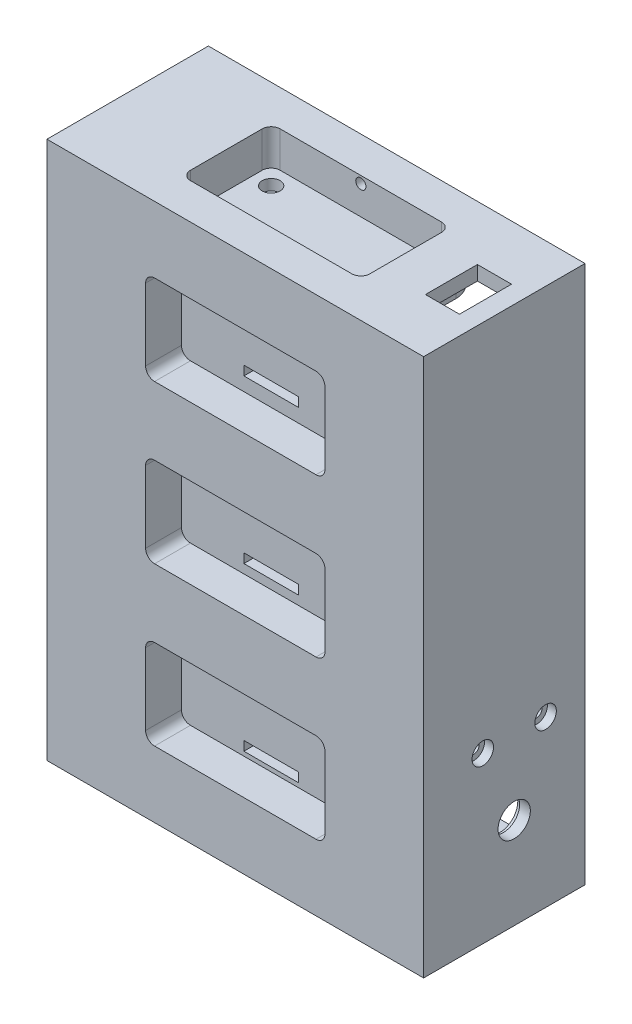
SolidWorks part; units mm, degrees
ref_plane "Спереди" through (0, 0, 0) normal (0, 0, 1) x (1, 0, 0)
ref_plane "Сверху" through (0, 0, 0) normal (0, 1, 0) x (1, 0, 0)
ref_plane "Справа" through (0, 0, 0) normal (1, 0, 0) x (0, 0, -1)
sketch "Эскиз1" plane through (0, 0, 0) normal (0, 0, 1) x (1, 0, 0)
  line L1 (-52.5, -75) -> (52.5, -75)
  line L2 (-52.5, -75) -> (-52.5, 75)
  line L3 (-52.5, 75) -> (52.5, 75)
  line L4 (52.5, -75) -> (52.5, 75)
  line L5 (-52.5, -75) -> (52.5, 75) construction
  line L6 (-52.5, 75) -> (52.5, -75) construction
  point P0 (0, 0)
  dimension "D1" = 105
  dimension "D2" = 150
extrude "Бобышка-Вытянуть1" add sketch "Эскиз1" along normal blind 45
sketch "Эскиз2" plane through (0, -75, 0) normal (0, -1, 0) x (1, 0, 0)
  line L0 (-1050, 22.5) -> (48950, 22.5) construction
  line L1 (-52.5, 45) -> (-52.5, 0) construction
  line L2 (0, -999.2777) -> (0, 49000.7223) construction
  line L4 (-22.5, 10) -> (22.5, 10)
  line L5 (-25, 12.5) -> (-25, 32.5)
  line L6 (-22.5, 35) -> (22.5, 35)
  line L7 (25, 12.5) -> (25, 32.5)
  line L8 (-25, 10) -> (25, 35) construction
  line L9 (-25, 35) -> (25, 10) construction
  arc A0 (-22.5, 35) -> (-25, 32.5) centre (-22.5, 32.5) ccw
  arc A1 (-25, 12.5) -> (-22.5, 10) centre (-22.5, 12.5) ccw
  arc A2 (25, 12.5) -> (22.5, 10) centre (22.5, 12.5) cw
  arc A3 (25, 32.5) -> (22.5, 35) centre (22.5, 32.5) ccw
  point P5 (-52.5, 22.5)
  point P6 (0, 22.5)
  point P12 (0, 22.5)
  dimension "D3" = 2.5
  dimension "D4" = 2.5
  dimension "D1" = 25
  dimension "D2" = 50
extrude "Вырез-Вытянуть1" cut sketch "Эскиз2" against normal blind 10
sketch "Эскиз4" plane through (0, 0, 45) normal (0, 0, 1) x (1, 0, 0)
  line L0 (0, -1000) -> (0, 49000) construction
  line L1 (-1000, 0) -> (49000, 0) construction
  line L2 (-22.5, 31.5) -> (22.5, 31.5)
  line L3 (-25, 34) -> (-25, 54)
  line L4 (-22.5, 56.5) -> (22.5, 56.5)
  line L5 (-22.5, -12.5) -> (22.5, -12.5)
  line L6 (-25, -10) -> (-25, 10)
  line L7 (-22.5, 12.5) -> (22.5, 12.5)
  line L8 (25, -10) -> (25, 10)
  line L9 (-25, -12.5) -> (25, 12.5) construction
  line L10 (-25, 12.5) -> (25, -12.5) construction
  line L11 (25, 34) -> (25, 54)
  line L12 (-25, 31.5) -> (25, 56.5) construction
  line L13 (-25, 56.5) -> (25, 31.5) construction
  line L14 (-25, -12.5) -> (25, -12.5) [skipped]
  line L15 (-25, -12.5) -> (-25, 12.5) [skipped]
  line L16 (-25, 12.5) -> (25, 12.5) [skipped]
  line L17 (25, -12.5) -> (25, 12.5) [skipped]
  line L18 (-25, -12.5) -> (25, 12.5) construction
  line L19 (-25, 12.5) -> (25, -12.5) construction
  line L20 (-22.5, -56.5) -> (22.5, -56.5)
  line L21 (-25, -54) -> (-25, -34)
  line L22 (-22.5, -31.5) -> (22.5, -31.5)
  line L23 (25, -54) -> (25, -34)
  line L24 (-25, -56.5) -> (25, -31.5) construction
  line L25 (-25, -31.5) -> (25, -56.5) construction
  arc A0 (22.5, -31.5) -> (25, -34) centre (22.5, -34) cw
  arc A1 (25, -54) -> (22.5, -56.5) centre (22.5, -54) cw
  arc A2 (-22.5, -56.5) -> (-25, -54) centre (-22.5, -54) cw
  arc A3 (-25, -34) -> (-22.5, -31.5) centre (-22.5, -34) cw
  arc A4 (-25, 54) -> (-22.5, 56.5) centre (-22.5, 54) cw
  arc A5 (-22.5, 12.5) -> (-25, 10) centre (-22.5, 10) ccw
  arc A6 (25, -10) -> (22.5, -12.5) centre (22.5, -10) cw
  arc A7 (22.5, 56.5) -> (25, 54) centre (22.5, 54) cw
  arc A8 (25, 34) -> (22.5, 31.5) centre (22.5, 34) cw
  arc A9 (-22.5, 31.5) -> (-25, 34) centre (-22.5, 34) cw
  arc A10 (22.5, 12.5) -> (25, 10) centre (22.5, 10) cw
  arc A11 (-22.5, -12.5) -> (-25, -10) centre (-22.5, -10) cw
  point P4 (25, 46.4046)
  point P6 (36.2514, -28.1819)
  point P7 (0, 0)
  point P8 (0, 0)
  point P9 (0, 44)
  point P18 (0, 0)
  point P23 (0, -44)
  point P28 (1.0897, -41.0449)
  point P29 (0, 43.0061)
  dimension "D7" = 2.5
  dimension "D8" = 2.5
  dimension "D1" = 25
  dimension "D2" = 50
  dimension "D5" = 31.5
  dimension "D6" = 31.5
  dimension "D3" = 2
  dimension "D4" = 2
extrude "Вырез-Вытянуть2" cut sketch "Эскиз4" against normal blind 10
mirror "Зеркальное отражение1" about plane through (0, 0, 0) normal (0, 1, 0) of "Вырез-Вытянуть1"
shell "Оболочка1" thickness 4 removed face at (0, 0, 0)
sketch "Эскиз5" plane through (-52.5, 0, 0) normal (-1, 0, 0) x (0, 0, 1)
  line L0 (-985.5789, -75) -> (49014.4211, -75) construction
  line L2 (-988.4344, -61) -> (49011.5656, -61) construction
  line L3 (45, -75) -> (0, -75) construction
  line L4 (-983.1093, -29) -> (49016.8907, -29) construction
  line L5 (0, 75) -> (0, -75) construction
  line L6 (19.75, -29) -> (19.75, -49.5) construction
  circle A0 centre (11, -29) radius 1.475
  circle A1 centre (28.5, -29) radius 1.475
  circle A2 centre (19.75, -49.5) radius 4.5
  dimension "D2" = 32
  dimension "D3" = 2.95
  dimension "D6" = 17.5
  dimension "D7" = 9
  dimension "D1" = 14
  dimension "D4" = 17.5
  dimension "D5" = 11
  dimension "D8" = 20.5
extrude "Вырез-Вытянуть3" cut sketch "Эскиз5" against normal blind 15
sketch "Эскиз6" plane through (-52.5, 0, 0) normal (-1, 0, 0) x (0, 0, 1)
  circle A0 centre (11, -29) radius 3
  circle A1 centre (28.5, -29) radius 3
  dimension "D1" = 6
  dimension "D2" = 17.5
extrude "Вырез-Вытянуть4" cut sketch "Эскиз6" against normal blind 2.5
sketch "Эскиз10" plane through (0, 0, 31) normal (0, 0, -1) x (-1, 0, 0)
  line L0 (-22.5, -27.5) -> (22.5, -27.5) construction
  line L1 (21, -27.5) -> (26, -27.5)
  line L2 (21, -27.5) -> (21, -64)
  line L3 (21, -64) -> (26, -64)
  line L4 (26, -27.5) -> (26, -64)
  line L5 (21, -27.5) -> (26, -64) construction
  line L6 (21, -64) -> (26, -27.5) construction
  line L7 (29, -34) -> (29, -54) construction
  point P4 (23.5, -45.75)
  dimension "D1" = 36.5
  dimension "D2" = 3
  dimension "D3" = 5
extrude "Вырез-Вытянуть15" cut sketch "Эскиз10" against normal blind 3 and the other way through all
sketch "Эскиз11" plane through (-48.5, 0, 0) normal (1, 0, 0) x (0, 0, -1)
  circle A0 centre (-19.75, -49.5) radius 5
  dimension "D1" = 10
extrude "Вырез-Вытянуть16" cut sketch "Эскиз11" against normal blind 1
mirror "Зеркальное отражение2" about plane through (0, 0, 0) normal (1, 0, 0) of "Вырез-Вытянуть16", "Вырез-Вытянуть15", "Вырез-Вытянуть4", "Вырез-Вытянуть3"
sketch "Эскиз12" plane through (0, 0, 6) normal (0, 0, -1) x (-1, 0, 0)
  line L0 (-1014.7864, -63) -> (48985.2136, -63) construction
  line L1 (21, -61) -> (-21, -61) construction
  line L2 (0, -1061) -> (0, 48939) construction
  line L3 (-10, -1061) -> (-10, 48939) construction
  line L4 (10, -1061) -> (10, 48939) construction
  circle A0 centre (-10, -63) radius 1.45
  circle A1 centre (10, -63) radius 1.45
  point P7 (0, -61)
  point P15 (10, -63)
  dimension "D4" = 2.9
  dimension "D1" = 2
  dimension "D2" = 20
  dimension "D3" = 10
extrude "Вырез-Вытянуть17" cut sketch "Эскиз12" against normal blind 10
sketch "Эскиз13" plane through (0, 0, 31) normal (0, 0, -1) x (-1, 0, 0)
  line L0 (-1008.6674, -29.5) -> (48991.3326, -29.5) construction
  line L1 (-22.5, -27.5) -> (22.5, -27.5) construction
  line L2 (0, -1027.5) -> (0, 48972.5) construction
  circle A0 centre (-9, -29.5) radius 1.45
  circle A1 centre (9, -29.5) radius 1.45
  point P7 (0, -27.5)
  dimension "D2" = 18
  dimension "D3" = 2.9
  dimension "D1" = 2
  dimension "D4" = 18
extrude "Вырез-Вытянуть18" cut sketch "Эскиз13" against normal blind 10
sketch "Эскиз14" plane through (0, 0, 31) normal (0, 0, -1) x (-1, 0, 0)
  line L0 (20, -957.2029) -> (20, 49042.7971) construction
  line L1 (29, 54) -> (29, 34) construction
  line L2 (-22.5, 60.5) -> (22.5, 60.5) construction
  line L3 (0, -972.5) -> (0, 49027.5) construction
  line L4 (22.5, 27.5) -> (-22.5, 27.5) construction
  line L5 (-20, -957.2029) -> (-20, 49042.7971) construction
  circle A0 centre (20, 48.5) radius 1.45
  circle A1 centre (20, -6.5) radius 1.45
  circle A2 centre (-20, -6.5) radius 1.45
  circle A3 centre (-20, 48.5) radius 1.45
  point P15 (0, 27.5)
  dimension "D1" = 2.9
  dimension "D3" = 9
  dimension "D2" = 55
  dimension "D4" = 12
extrude "Вырез-Вытянуть19" cut sketch "Эскиз14" against normal blind 3
sketch "Эскиз15" plane through (0, 0, 35) normal (0, 0, 1) x (1, 0, 0)
  line L0 (-1010.1672, -54) -> (48989.8328, -54) construction
  line L1 (0, -1031.5) -> (0, 48968.5) construction
  line L2 (-7.6, -55.3) -> (7.6, -55.3)
  line L3 (-7.6, -55.3) -> (-7.6, -52.7)
  line L4 (-7.6, -52.7) -> (7.6, -52.7)
  line L5 (7.6, -55.3) -> (7.6, -52.7)
  line L6 (-7.6, -55.3) -> (7.6, -52.7) construction
  line L7 (-7.6, -52.7) -> (7.6, -55.3) construction
  line L8 (22.5, -31.5) -> (-22.5, -31.5) construction
  line L9 (-22.5, -56.5) -> (22.5, -56.5) construction
  line L10 (-7.6, -10) -> (7.6, -10)
  line L11 (-7.6, -10) -> (-7.6, -7.4)
  line L12 (-7.6, -7.4) -> (7.6, -7.4)
  line L13 (7.6, -10) -> (7.6, -7.4)
  line L14 (-7.6, -10) -> (7.6, -7.4) construction
  line L15 (-7.6, -7.4) -> (7.6, -10) construction
  line L16 (-7.6, 35.3) -> (7.6, 35.3)
  line L17 (-7.6, 35.3) -> (-7.6, 37.9)
  line L18 (-7.6, 37.9) -> (7.6, 37.9)
  line L19 (7.6, 35.3) -> (7.6, 37.9)
  line L20 (-7.6, 35.3) -> (7.6, 37.9) construction
  line L21 (-7.6, 37.9) -> (7.6, 35.3) construction
  line L22 (-22.5, -12.5) -> (22.5, -12.5) construction
  line L23 (22.5, 12.5) -> (-22.5, 12.5) construction
  circle A0 centre (-20, -36.5) radius 2.5
  circle A1 centre (20, -36.5) radius 2.5
  circle A2 centre (-20, 7.5) radius 2.5
  circle A3 centre (20, 7.5) radius 2.5
  circle A4 centre (-20, 51.5) radius 2.5
  circle A5 centre (20, 51.5) radius 2.5
  point P1 (0, -54)
  point P12 (0, -31.5)
  point P16 (0, -8.7)
  point P21 (0, 36.6)
  point P30 (-20, 7.508)
  dimension "D6" = 40
  dimension "D8" = 5
  dimension "D1" = 2.6
  dimension "D2" = 15.2
  dimension "D3" = 2.5
  dimension "D4" = 3
  dimension "D5" = 2.5
  dimension "D7" = 40
  dimension "D9" = 5
  dimension "D10" = 3
  dimension "D11" = 5
extrude "Вырез-Вытянуть20" cut sketch "Эскиз15" against normal blind 3
sketch "Эскиз16" plane through (0, 0, 32) normal (0, 0, 1) x (1, 0, 0)
  line L0 (-7.6, -54) -> (7.6, -54) construction
  line L1 (-7.6, -52.7) -> (-7.6, -55.3) construction
  line L2 (7.6, -55.3) -> (7.6, -52.7) construction
  line L3 (0, -1000) -> (0, 49000) construction
  line L4 (-7, -54.9) -> (7, -54.9)
  line L5 (-7, -54.9) -> (-7, -53.1)
  line L6 (-7, -53.1) -> (7, -53.1)
  line L7 (7, -54.9) -> (7, -53.1)
  line L8 (-7, -54.9) -> (7, -53.1) construction
  line L9 (-7, -53.1) -> (7, -54.9) construction
  line L10 (-7, -9.6) -> (7, -9.6)
  line L11 (-7, -9.6) -> (-7, -7.8)
  line L12 (-7, -7.8) -> (7, -7.8)
  line L13 (7, -9.6) -> (7, -7.8)
  line L14 (-7.6, -8.7) -> (7.6, -8.7) construction
  line L15 (-7, -9.6) -> (7, -7.8) construction
  line L16 (-7, -7.8) -> (7, -9.6) construction
  line L17 (-7, 35.7) -> (7, 35.7)
  line L18 (-7, 35.7) -> (-7, 37.5)
  line L19 (-7, 37.5) -> (7, 37.5)
  line L20 (7, 35.7) -> (7, 37.5)
  line L21 (-7.6, 36.6) -> (7.6, 36.6) construction
  line L22 (-7, 35.7) -> (7, 37.5) construction
  line L23 (-7, 37.5) -> (7, 35.7) construction
  line L24 (-7.6, -7.4) -> (-7.6, -10) construction
  point P6 (0, -54)
  point P12 (0, -30.9154)
  point P17 (0, -8.7)
  point P24 (0, 36.6)
  point P29 (0, -14.6748)
  point P30 (0, -9.0247)
  point P31 (-7.6, -8.7)
  dimension "D1" = 1.8
  dimension "D2" = 14
  dimension "D3" = 3
extrude "Вырез-Вытянуть21" cut sketch "Эскиз16" against normal blind 3
sketch "Эскиз17" plane through (0, -65, 0) normal (0, -1, 0) x (1, 0, 0)
  line L0 (-7.6, 12.5) -> (7.6, 12.5)
  line L1 (-7.6, 12.5) -> (-7.6, 15.1)
  line L2 (-7.6, 15.1) -> (7.6, 15.1)
  line L3 (7.6, 12.5) -> (7.6, 15.1)
  line L4 (-7.6, 12.5) -> (7.6, 15.1) construction
  line L5 (-7.6, 15.1) -> (7.6, 12.5) construction
  line L6 (-22.5, 10) -> (22.5, 10) construction
  line L7 (22.5, 35) -> (-22.5, 35) construction
  line L9 (0, -965) -> (0, 49035) construction
  line L10 (22.5, 35) -> (-22.5, 35) construction
  circle A0 centre (-20, 30) radius 2.5
  circle A1 centre (20, 30) radius 2.5
  point P0 (0, 13.8)
  point P13 (0, 13.8)
  point P14 (-8.8823, 15.1)
  point P16 (0, 13.8)
  point P20 (0, 35)
  dimension "D5" = 5
  dimension "D1" = 2.6
  dimension "D2" = 15.2
  dimension "D3" = 40
  dimension "D4" = 40
  dimension "D6" = 2.5
  dimension "D7" = 5
extrude "Вырез-Вытянуть22" cut sketch "Эскиз17" against normal blind 3
sketch "Эскиз18" plane through (0, -62, 0) normal (0, -1, 0) x (1, 0, 0)
  line L0 (-7.6, 13.8) -> (7.6, 13.8) construction
  line L1 (-7.6, 15.1) -> (-7.6, 12.5) construction
  line L2 (7.6, 12.5) -> (7.6, 15.1) construction
  line L4 (-7, 12.9) -> (7, 12.9)
  line L5 (-7, 12.9) -> (-7, 14.7)
  line L6 (-7, 14.7) -> (7, 14.7)
  line L7 (7, 12.9) -> (7, 14.7)
  line L8 (-7, 12.9) -> (7, 14.7) construction
  line L9 (-7, 14.7) -> (7, 12.9) construction
  point P6 (0, 13.8)
  dimension "D1" = 1.8
  dimension "D2" = 14
extrude "Вырез-Вытянуть23" cut sketch "Эскиз18" against normal blind 3
sketch "Эскиз19" plane through (0, 65, 0) normal (0, 1, 0) x (1, 0, 0)
  line L0 (-7.6, -32.5) -> (7.6, -32.5)
  line L1 (-7.6, -32.5) -> (-7.6, -29.9)
  line L2 (-7.6, -29.9) -> (7.6, -29.9)
  line L3 (7.6, -32.5) -> (7.6, -29.9)
  line L4 (-7.6, -32.5) -> (7.6, -29.9) construction
  line L5 (-7.6, -29.9) -> (7.6, -32.5) construction
  line L6 (0, -1010) -> (0, 48990) construction
  line L7 (-22.5, -10) -> (22.5, -10) construction
  line L8 (22.5, -35) -> (-22.5, -35) construction
  circle A0 centre (-20, -15) radius 2.5
  circle A1 centre (20, -15) radius 2.5
  point P0 (0, -31.2)
  point P14 (0, -10)
  point P16 (0, -31.2)
  point P17 (0, 0)
  dimension "D5" = 5
  dimension "D7" = 5
  dimension "D1" = 2.6
  dimension "D2" = 15.2
  dimension "D3" = 40
  dimension "D4" = 40
  dimension "D6" = 2.5
extrude "Вырез-Вытянуть24" cut sketch "Эскиз19" against normal blind 3
sketch "Эскиз20" plane through (0, 62, 0) normal (0, 1, 0) x (1, 0, 0)
  line L0 (-1007.6, -31.2) -> (48992.4, -31.2) construction
  line L1 (-7.6, -29.9) -> (-7.6, -32.5) construction
  line L3 (-7, -32.1) -> (7, -32.1)
  line L4 (-7, -32.1) -> (-7, -30.3)
  line L5 (-7, -30.3) -> (7, -30.3)
  line L6 (7, -32.1) -> (7, -30.3)
  line L7 (-7, -32.1) -> (7, -30.3) construction
  line L8 (-7, -30.3) -> (7, -32.1) construction
  line L10 (0, -1029.9) -> (0, 48970.1) construction
  line L11 (7.6, -29.9) -> (-7.6, -29.9) construction
  point P1 (0, -31.2)
  point P5 (-7.6, -31.2)
  point P10 (0, -31.2)
  point P18 (0, -29.9)
  dimension "D1" = 1.8
  dimension "D2" = 14
extrude "Вырез-Вытянуть25" cut sketch "Эскиз20" against normal blind 3
sketch "Эскиз21" plane through (0, 75, 0) normal (0, 1, 0) x (1, 0, 0)
  line L0 (-975, -22.5) -> (49025, -22.5) construction
  line L1 (37.75, -29.75) -> (47.25, -29.75)
  line L2 (37.75, -29.75) -> (37.75, -15.25)
  line L3 (37.75, -15.25) -> (47.25, -15.25)
  line L4 (47.25, -29.75) -> (47.25, -15.25)
  line L5 (37.75, -29.75) -> (47.25, -15.25) construction
  line L6 (37.75, -15.25) -> (47.25, -29.75) construction
  line L7 (25, -12.5) -> (25, -32.5) construction
  line L8 (42.5, -1022.5) -> (42.5, 48977.5) construction
  line L9 (52.5, -45) -> (52.5, 0) construction
  point P0 (42.5, -22.5)
  point P10 (25, -22.5)
  dimension "D1" = 9.5
  dimension "D2" = 14.5
  dimension "D3" = 10
extrude "Вырез-Вытянуть26" cut sketch "Эскиз21" against normal blind 4
sketch "Эскиз22" plane through (0, 0, 0) normal (0, 0, -1) x (-1, 0, 0)
  line L0 (-50.5, -925) -> (-50.5, 49075) construction
  line L2 (-52.5, -75) -> (-52.5, 75) construction
  line L3 (-1046.2998, 73) -> (48953.7002, 73) construction
  line L4 (-52.5, 75) -> (52.5, 75) construction
  line L5 (50.5, -925) -> (50.5, 49075) construction
  line L6 (52.5, 75) -> (52.5, -75) construction
  line L7 (-1052.5, -73) -> (48947.5, -73) construction
  line L8 (52.5, -75) -> (-52.5, -75) construction
  line L9 (0, -925) -> (0, 49075) construction
  line L10 (-1052.5, 0) -> (48947.5, 0) construction
  circle A0 centre (-50.5, -73) radius 1.425
  circle A1 centre (-50.5, 73) radius 1.425
  circle A2 centre (50.5, 73) radius 1.425
  circle A3 centre (50.5, -73) radius 1.425
  circle A4 centre (0, 73) radius 1.425
  circle A5 centre (0, -73) radius 1.425
  circle A6 centre (-50.5, 0) radius 1.425
  circle A7 centre (50.5, 0) radius 1.425
  point P27 (0, 75)
  point P34 (-52.5, 0)
  dimension "D5" = 2.85
  dimension "D1" = 2
  dimension "D2" = 2
  dimension "D3" = 2
  dimension "D4" = 2
extrude "Вырез-Вытянуть27" cut sketch "Эскиз22" against normal blind 10
